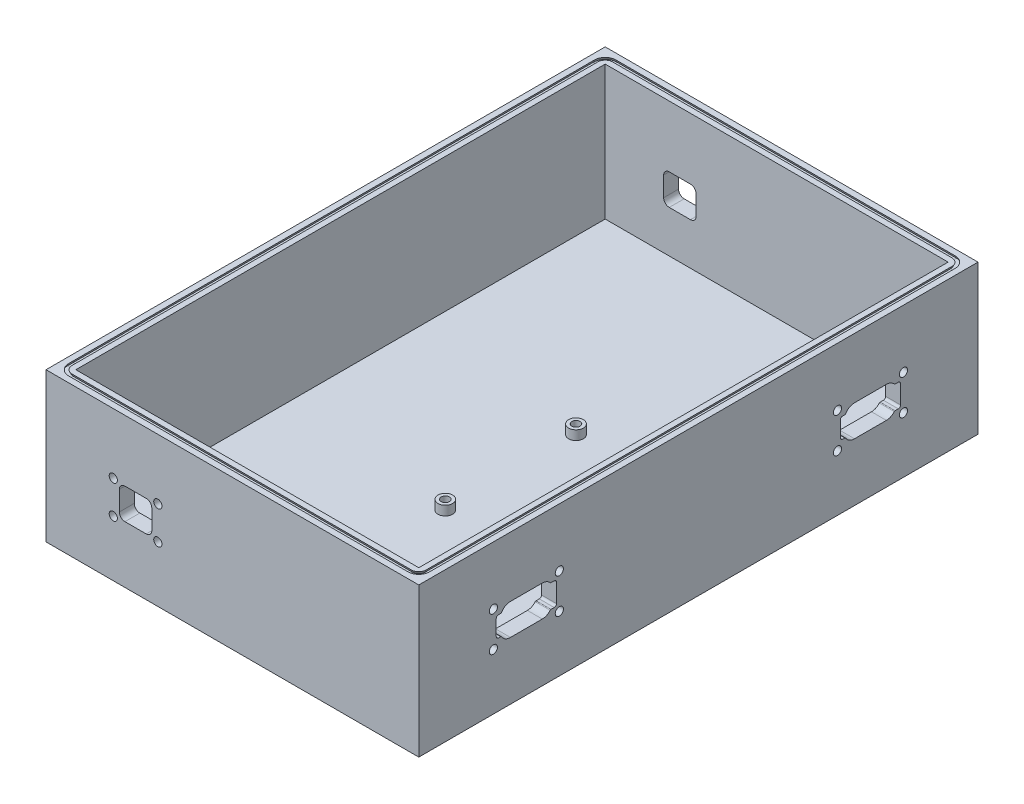
SolidWorks part; units mm, degrees
ref_plane "Front Plane" through (0, 0, 0) normal (0, 0, 1) x (1, 0, 0)
ref_plane "Top Plane" through (0, 0, 0) normal (0, 1, 0) x (1, 0, 0)
ref_plane "Right Plane" through (0, 0, 0) normal (1, 0, 0) x (0, 0, -1)
sketch "Sketch1" plane through (0, 0, 0) normal (0, 1, 0) x (1, 0, 0)
  line L1 (0, 0) -> (254, 0)
  line L2 (0, 0) -> (0, 381)
  line L3 (0, 381) -> (254, 381)
  line L4 (254, 0) -> (254, 381)
  dimension "D1" = 254
  dimension "D2" = 381
extrude "Boss-Extrude1" add sketch "Sketch1" along normal blind 101.6
sketch "12 pin hole" [suppressed] plane through (254, 0, 0) normal (1, 0, 0) x (0, 0, -1)
  line L8 (50.8, 10.16) -> (95.758, 10.16) construction
  line L9 (50.8, 10.16) -> (50.8, 34.036) construction
  line L10 (50.8, 34.036) -> (95.758, 34.036) construction
  line L11 (95.758, 10.16) -> (95.758, 34.036) construction
  line L12 (55.7357, 28.956) -> (54.2925, 28.956)
  line L13 (52.7685, 27.432) -> (52.7685, 16.764)
  line L14 (54.2925, 15.24) -> (55.7357, 15.24)
  line L16 (90.087, 29.972) -> (92.2655, 29.972)
  line L17 (93.7895, 28.448) -> (93.7895, 15.748)
  line L18 (92.2655, 14.224) -> (90.087, 14.224)
  line L21 (62.4205, 25.654) -> (84.1375, 25.654) construction
  line L22 (62.4205, 25.654) -> (62.4205, 18.542) construction
  line L23 (62.4205, 18.542) -> (84.1375, 18.542) construction
  line L24 (84.1375, 25.654) -> (84.1375, 18.542) construction
  line L25 (62.4205, 32.7152) -> (84.1375, 32.7152)
  line L26 (62.4205, 11.4808) -> (84.1375, 11.4808)
  line L27 (52.7685, 22.098) -> (50.8, 22.098) construction
  line L28 (93.7895, 22.098) -> (95.758, 22.098) construction
  arc A4 (62.4205, 32.7152) -> (56.3868, 29.3222) centre (62.4205, 25.654) ccw
  arc A5 (89.5075, 30.2392) -> (84.1375, 32.7152) centre (84.1375, 25.654) ccw
  arc A6 (62.4205, 11.4808) -> (56.3868, 14.8738) centre (62.4205, 18.542) cw
  arc A7 (89.5075, 13.9568) -> (84.1375, 11.4808) centre (84.1375, 18.542) cw
  arc A8 (90.087, 29.972) -> (89.5075, 30.2392) centre (90.087, 30.734) cw
  arc A9 (90.087, 14.224) -> (89.5075, 13.9568) centre (90.087, 13.462) ccw
  arc A10 (55.7357, 15.24) -> (56.3868, 14.8738) centre (55.7357, 14.478) cw
  arc A11 (55.7357, 28.956) -> (56.3868, 29.3222) centre (55.7357, 29.718) ccw
  arc A12 (92.2655, 29.972) -> (93.7895, 28.448) centre (92.2655, 28.448) cw
  arc A13 (93.7895, 15.748) -> (92.2655, 14.224) centre (92.2655, 15.748) cw
  arc A14 (52.7685, 16.764) -> (54.2925, 15.24) centre (54.2925, 16.764) ccw
  arc A15 (54.2925, 28.956) -> (52.7685, 27.432) centre (54.2925, 27.432) ccw
  point P25 (50.8, 22.098)
  point P28 (52.7685, 22.098)
  point P29 (93.7895, 22.098)
  point P34 (62.4205, 22.098)
  point P35 (84.1375, 22.098)
  point P44 (73.279, 10.16)
  point P46 (73.279, 11.4808)
  point P59 (93.7895, 29.972)
  point P62 (93.7895, 14.224)
  point P65 (52.7685, 15.24)
  point P68 (52.7685, 28.956)
  dimension "D4" = 41.021
  dimension "D5" = 15.748
  dimension "D11" = 7.0612
  dimension "D12" = 0.762
  dimension "D13" = 1.524
  dimension "D1" = 44.958
  dimension "D2" = 23.876
  dimension "D8" = 13.716
  dimension "D9" = 21.2344
  dimension "D10" = 21.717
sketch "Sketch2" plane through (0, 101.6, 0) normal (0, 1, 0) x (1, 0, 0)
  line L0 (0, 381) -> (0, 0) construction
  line L1 (10.16, 10.16) -> (243.84, 10.16)
  line L2 (10.16, 10.16) -> (10.16, 370.84)
  line L3 (10.16, 370.84) -> (243.84, 370.84)
  line L4 (243.84, 10.16) -> (243.84, 370.84)
  line L5 (254, 381) -> (0, 381) construction
  line L6 (254, 0) -> (254, 381) construction
  line L7 (0, 0) -> (254, 0) construction
  dimension "D1" = 10.16
  dimension "D2" = 10.16
  dimension "D3" = 10.16
  dimension "D4" = 10.16
extrude "Cut-Extrude1" cut sketch "Sketch2" against normal blind 91.44
ref_plane "Plane1" through (0, 101.6, 0) normal (0, 1, 0) x (1, 0, 0)
sketch "Sketch3" plane through (0, 101.6, 0) normal (0, 1, 0) x (1, 0, 0)
  line L4 (6.35, 11.43) -> (6.35, 369.57)
  line L5 (243.84, 370.84) -> (10.16, 370.84) construction
  line L6 (10.16, 370.84) -> (10.16, 10.16) construction
  line L7 (243.84, 10.16) -> (243.84, 370.84) construction
  line L8 (10.16, 10.16) -> (243.84, 10.16) construction
  line L13 (11.43, 374.65) -> (242.57, 374.65)
  line L14 (247.65, 369.57) -> (247.65, 11.43)
  line L15 (242.57, 6.35) -> (11.43, 6.35)
  arc A0 (6.35, 369.57) -> (11.43, 374.65) centre (11.43, 369.57) cw
  arc A1 (242.57, 374.65) -> (247.65, 369.57) centre (242.57, 369.57) cw
  arc A2 (247.65, 11.43) -> (242.57, 6.35) centre (242.57, 11.43) cw
  arc A3 (11.43, 6.35) -> (6.35, 11.43) centre (11.43, 11.43) cw
  dimension "D5" = 5.08
  dimension "D1" = 3.81
  dimension "D2" = 3.81
  dimension "D3" = 3.81
  dimension "D4" = 3.81
ref_plane "Plane2" through (0, 0, 0) normal (0, 0, 1) x (1, 0, 0)
ref_plane "Plane3" through (0, 0, -15.24) normal (0, 0, 1) x (1, 0, 0)
sketch "Sketch4" plane through (0, 0, -15.24) normal (0, 0, 1) x (1, 0, 0)
  line L0 (4.064, 101.6) -> (3.2724, 99.822)
  line L1 (6.35, 101.6) -> (7.1416, 99.822)
  line L2 (3.2724, 99.822) -> (7.1416, 99.822)
  line L5 (4.064, 101.6) -> (6.35, 101.6)
  dimension "D1" = 1.778
  dimension "D2" = 2.286
  dimension "D3" = 66
  dimension "D4" = 66
sweep "Cut-Sweep2" cut profiles "Sketch4" path "Sketch3"
sketch "Sketch13" plane through (254, 0, 0) normal (1, 0, 0) x (0, 0, -1)
  line L0 (50.8, 38.1) -> (50.8, 0) construction
  line L1 (0, 0) -> (381, 0) construction
  line L2 (50.8, 38.1) -> (0, 38.1) construction
  line L3 (0, 101.6) -> (0, 0) construction
  line L4 (330.2, 0) -> (330.2, 38.1) construction
  line L5 (330.2, 38.1) -> (381, 38.1) construction
  line L6 (381, 101.6) -> (381, 0) construction
  line B0 (50.8, 38.1) -> (95.758, 38.1) construction
  line B1 (50.8, 38.1) -> (50.8, 61.976) construction
  line B2 (50.8, 61.976) -> (95.758, 61.976) construction
  line B3 (95.758, 38.1) -> (95.758, 61.976) construction
  line B4 (55.7357, 56.896) -> (54.2925, 56.896)
  line B5 (52.7685, 55.372) -> (52.7685, 44.704)
  line B6 (54.2925, 43.18) -> (55.7357, 43.18)
  line B7 (90.087, 57.912) -> (92.2655, 57.912)
  line B8 (93.7895, 56.388) -> (93.7895, 43.688)
  line B9 (92.2655, 42.164) -> (90.087, 42.164)
  line B10 (62.4205, 60.6552) -> (84.1375, 60.6552)
  line B11 (62.4205, 39.4208) -> (84.1375, 39.4208)
  arc B12 (62.4205, 60.6552) -> (56.3868, 57.2622) centre (62.4205, 53.594) ccw
  arc B13 (89.5075, 58.1792) -> (84.1375, 60.6552) centre (84.1375, 53.594) ccw
  arc B14 (62.4205, 39.4208) -> (56.3868, 42.8138) centre (62.4205, 46.482) cw
  arc B15 (89.5075, 41.8968) -> (84.1375, 39.4208) centre (84.1375, 46.482) cw
  arc B16 (90.087, 57.912) -> (89.5075, 58.1792) centre (90.087, 58.674) cw
  arc B17 (90.087, 42.164) -> (89.5075, 41.8968) centre (90.087, 41.402) ccw
  arc B18 (55.7357, 43.18) -> (56.3868, 42.8138) centre (55.7357, 42.418) cw
  arc B19 (55.7357, 56.896) -> (56.3868, 57.2622) centre (55.7357, 57.658) ccw
  arc B20 (92.2655, 57.912) -> (93.7895, 56.388) centre (92.2655, 56.388) cw
  arc B21 (93.7895, 43.688) -> (92.2655, 42.164) centre (92.2655, 43.688) cw
  arc B22 (52.7685, 44.704) -> (54.2925, 43.18) centre (54.2925, 44.704) ccw
  arc B23 (54.2925, 56.896) -> (52.7685, 55.372) centre (54.2925, 55.372) ccw
  line B24 (285.242, 38.1) -> (330.2, 38.1) construction
  line B25 (285.242, 38.1) -> (285.242, 61.976) construction
  line B26 (285.242, 61.976) -> (330.2, 61.976) construction
  line B27 (330.2, 38.1) -> (330.2, 61.976) construction
  line B28 (290.1777, 56.896) -> (288.7345, 56.896)
  line B29 (287.2105, 55.372) -> (287.2105, 44.704)
  line B30 (288.7345, 43.18) -> (290.1777, 43.18)
  line B31 (324.529, 57.912) -> (326.7075, 57.912)
  line B32 (328.2315, 56.388) -> (328.2315, 43.688)
  line B33 (326.7075, 42.164) -> (324.529, 42.164)
  line B34 (296.8625, 60.6552) -> (318.5795, 60.6552)
  line B35 (296.8625, 39.4208) -> (318.5795, 39.4208)
  arc B36 (296.8625, 60.6552) -> (290.8288, 57.2622) centre (296.8625, 53.594) ccw
  arc B37 (323.9495, 58.1792) -> (318.5795, 60.6552) centre (318.5795, 53.594) ccw
  arc B38 (296.8625, 39.4208) -> (290.8288, 42.8138) centre (296.8625, 46.482) cw
  arc B39 (323.9495, 41.8968) -> (318.5795, 39.4208) centre (318.5795, 46.482) cw
  arc B40 (324.529, 57.912) -> (323.9495, 58.1792) centre (324.529, 58.674) cw
  arc B41 (324.529, 42.164) -> (323.9495, 41.8968) centre (324.529, 41.402) ccw
  arc B42 (290.1777, 43.18) -> (290.8288, 42.8138) centre (290.1777, 42.418) cw
  arc B43 (290.1777, 56.896) -> (290.8288, 57.2622) centre (290.1777, 57.658) ccw
  arc B44 (326.7075, 57.912) -> (328.2315, 56.388) centre (326.7075, 56.388) cw
  arc B45 (328.2315, 43.688) -> (326.7075, 42.164) centre (326.7075, 43.688) cw
  arc B46 (287.2105, 44.704) -> (288.7345, 43.18) centre (288.7345, 44.704) ccw
  arc B47 (288.7345, 56.896) -> (287.2105, 55.372) centre (288.7345, 55.372) ccw
  dimension "D1" = 50.8
  dimension "D2" = 38.1
sketch_block_instance "Block7-3"
sketch_block "Block7" parameters "D6"=7.0612, "D7"=0.762, "D8"=1.524, "D1"=44.958, "D2"=23.876, "D3"=41.021, "D4"=21.2344, "D5"=21.717
sketch_block_instance "Block7-4"
extrude "Cut-Extrude10" cut sketch "Sketch13" against normal up to next
sketch "12 pin mount" plane through (254, 0, 0) normal (1, 0, 0) x (0, 0, -1)
  circle A0 centre (95.758, 61.976) radius 2.8
  circle A1 centre (95.758, 38.1) radius 2.8
  circle A2 centre (50.8, 38.1) radius 2.8
  circle A3 centre (50.8, 61.976) radius 2.8
  circle A4 centre (285.242, 61.976) radius 2.8
  circle A5 centre (330.2, 61.976) radius 2.8
  circle A6 centre (330.2, 38.1) radius 2.8
  circle A7 centre (285.242, 38.1) radius 2.8
  dimension "D1" = 5.6
extrude "Cut-Extrude3" cut sketch "12 pin mount" against normal blind 5.5
sketch "4 pin connector" plane through (0, 0, 0) normal (0, 0, 1) x (1, 0, 0)
  line L0 (76.2, 0) -> (76.2, 38.1) construction
  line L1 (0, 0) -> (254, 0) construction
  line L2 (76.2, 38.1) -> (254, 38.1) construction
  line L3 (254, 101.6) -> (254, 0) construction
  line L5 (45.847, 60.5536) -> (76.2, 60.5536) construction
  line L6 (45.847, 60.5536) -> (45.847, 38.1) construction
  line L7 (45.847, 38.1) -> (76.2, 38.1) construction
  line L8 (76.2, 60.5536) -> (76.2, 38.1) construction
  line L9 (53.7845, 59.817) -> (68.2625, 59.817)
  line L10 (49.9745, 56.007) -> (49.9745, 42.6466)
  line L11 (53.7845, 38.8366) -> (68.2625, 38.8366)
  line L12 (72.0725, 56.007) -> (72.0725, 42.6466)
  line L13 (61.0235, 38.8366) -> (61.0235, 59.817) construction
  line L14 (49.9745, 49.3268) -> (72.0725, 49.3268) construction
  arc A0 (68.2625, 59.817) -> (72.0725, 56.007) centre (68.2625, 56.007) cw
  arc A1 (68.2625, 38.8366) -> (72.0725, 42.6466) centre (68.2625, 42.6466) ccw
  arc A2 (49.9745, 42.6466) -> (53.7845, 38.8366) centre (53.7845, 42.6466) ccw
  arc A3 (53.7845, 59.817) -> (49.9745, 56.007) centre (53.7845, 56.007) ccw
  point P4 (61.0235, 49.3268)
  point P12 (61.0235, 38.1)
  point P15 (76.2, 49.3268)
  point P20 (72.0725, 59.817)
  point P24 (72.0725, 38.8366)
  point P29 (49.9745, 59.817)
  dimension "D1" = 22.098
  dimension "D7" = 3.81
  dimension "D2" = 22.4536
  dimension "D3" = 30.353
  dimension "D4" = 38.1
  dimension "D5" = 177.8
  dimension "D6" = 20.9804
extrude "Cut-Extrude5" cut sketch "4 pin connector" against normal up to next
extrude "Cut-Extrude6" cut sketch "Sketch5<2>" along normal up to next from surface starting at face at (127, 50.8, -381)
sketch "Sketch5<2>" plane through (0, 0, 0) normal (0, 0, 1) x (1, 0, 0) same geometry as "4 pin connector"
sketch "Sketch6" plane through (0, 0, 0) normal (0, 0, 1) x (1, 0, 0)
  circle A0 centre (76.2, 60.5536) radius 2.8
  circle A1 centre (76.2, 38.1) radius 2.8
  circle A2 centre (45.847, 38.1) radius 2.8
  circle A3 centre (45.847, 60.5536) radius 2.8
  dimension "D1" = 5.6
extrude "Cut-Extrude7" cut sketch "Sketch6" against normal blind 5.5
extrude "Cut-Extrude8" cut sketch "Sketch6<2>" along normal blind 5.5 from surface starting at face at (61.0235, 49.3268, -381)
sketch "Sketch6<2>" plane through (0, 0, 0) normal (0, 0, 1) x (1, 0, 0) same geometry as "Sketch6"
sketch "Sketch7" plane through (0, 10.16, 0) normal (0, 1, 0) x (1, 0, 0)
  line L0 (193.04, 189.1889) -> (243.84, 189.1889) construction
  line L1 (243.84, 10.16) -> (243.84, 370.84) construction
  line L5 (193.04, 144.6739) -> (127.38, 144.6739) construction
  line L6 (193.04, 144.6739) -> (193.04, 233.7039) construction
  line L7 (193.04, 233.7039) -> (127.38, 233.7039) construction
  line L8 (127.38, 144.6739) -> (127.38, 233.7039) construction
  circle A0 centre (127.38, 144.6739) radius 5
  circle A1 centre (193.04, 144.6739) radius 5
  circle A2 centre (193.04, 233.7039) radius 5
  circle A3 centre (127.38, 233.7039) radius 5
  dimension "D1" = 10
  dimension "D2" = 89.03
  dimension "D3" = 65.66
  dimension "D4" = 50.8
sketch "Sketch8" plane through (0, 10.16, 0) normal (0, 1, 0) x (1, 0, 0)
  circle A0 centre (127.38, 233.7039) radius 2.8
  circle A1 centre (193.04, 233.7039) radius 2.8
  circle A2 centre (193.04, 144.6739) radius 2.8
  circle A3 centre (127.38, 144.6739) radius 2.8
  dimension "D1" = 5.6
extrude "Boss-Extrude2" add sketch "Sketch7" along normal blind 6.35
extrude "Cut-Extrude9" cut sketch "Sketch8" against normal blind 5.5 from surface starting at face at (193.04, 16.51, -139.6739)
equation "\"M4 insert  width\"= 5.6mm"
equation "\"M4 insert  depth\"= 5.5mm"
equation "\"depth\"=0.1"
